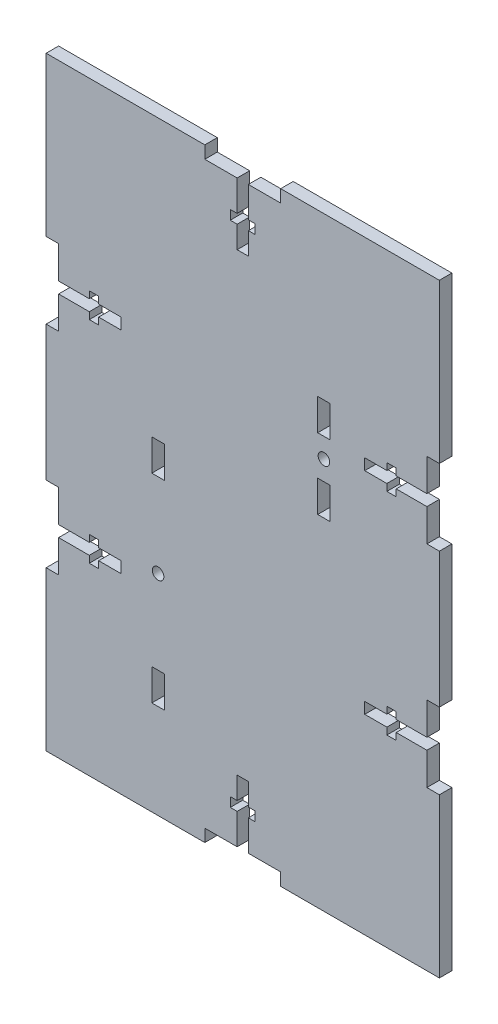
SolidWorks part; units mm, degrees
ref_plane "Front Plane" through (0, 0, 0) normal (0, 0, 1) x (1, 0, 0)
ref_plane "Top Plane" through (0, 0, 0) normal (0, 1, 0) x (1, 0, 0)
ref_plane "Right Plane" through (0, 0, 0) normal (1, 0, 0) x (0, 0, -1)
sketch "Sketch1" plane through (0, 0, 0) normal (0, 0, 1) x (1, 0, 0)
  line L0 (-50, 76.825) -> (-16.6667, 76.825)
  line L1 (-50, -76.825) -> (50, -76.825)
  line L2 (-50, -76.825) -> (-50, 76.825)
  line L3 (-50, 76.825) -> (50, 76.825) construction
  line L4 (50, -76.825) -> (50, 76.825)
  line L5 (-50, -76.825) -> (50, 76.825) construction
  line L6 (-50, 76.825) -> (50, -76.825) construction
  line L7 (-16.6667, 76.825) -> (16.6667, 76.825)
  line L8 (16.6667, 76.825) -> (50, 76.825)
  point P0 (0, 0)
  dimension "D1" = 100
  dimension "D2" = 153.65
extrude "Boss-Extrude1" add sketch "Sketch1" along normal blind 3.18
sketch "Sketch3" [suppressed] plane through (0, 0, 0) normal (0, 0, -1) x (-1, 0, 0)
  line L0 (-32.675, 34.075) -> (-32.675, -61.675)
  line L1 (-32.675, -61.675) -> (32.675, -61.675)
  line L2 (32.675, -61.675) -> (32.675, 34.075)
  line L3 (32.675, 34.075) -> (9.5, 34.075)
  line L4 (9.5, 34.075) -> (9.5, 37.075)
  line L5 (9.5, 37.075) -> (-9.5, 37.075)
  line L6 (-9.5, 37.075) -> (-9.5, 34.075)
  line L7 (-9.5, 34.075) -> (-32.675, 34.075)
  line L8 (32.675, 44.075) -> (-32.675, 44.075)
  line L9 (32.675, -61.675) -> (32.675, 44.075)
  line L10 (-32.675, -61.675) -> (32.675, -61.675)
  line L11 (-32.675, 44.075) -> (-32.675, -61.675)
  line L12 (-32.675, -61.675) -> (-32.675, -73.645) construction
  line L13 (44.645, -73.645) -> (-44.645, -73.645) construction
  line L14 (-32.675, -61.675) -> (-44.645, -61.675) construction
  line L15 (-44.645, -73.645) -> (-44.645, 73.645) construction
  line L16 (32.675, -61.675) -> (44.645, -61.675) construction
  line L17 (44.645, 73.645) -> (44.645, -73.645) construction
  dimension "D1" = 65.35
  dimension "D2" = 95.75
  dimension "D3" = 105.75
  dimension "D4" = 19
  dimension "D5" = 3
extrude "Cut-Extrude1" [suppressed] cut sketch "Sketch3" against normal through all contours L6 L7 L0 L1 L2 L3 L4 L5
sketch "Sketch9" [suppressed] plane through (-44.645, 0, 0) normal (-1, 0, 0) x (0, 0, 1)
  line L0 (0, 0) -> (3.18, 0) construction
  line L1 (0, 73.645) -> (0, -73.645) construction
  line L2 (3.18, 73.645) -> (3.18, -73.645) construction
  line L4 (0, -9.65) -> (3.18, -9.65)
  line L5 (0, -9.65) -> (0, 9.65)
  line L6 (0, 9.65) -> (3.18, 9.65)
  line L7 (3.18, -9.65) -> (3.18, 9.65)
  line L8 (0, -9.65) -> (3.18, 9.65) construction
  line L9 (0, 9.65) -> (3.18, -9.65) construction
  point P6 (1.59, 0)
  dimension "D1" = 19.3
extrude "Boss-Extrude4" [suppressed] add sketch "Sketch9" along normal blind 3.18
sketch "Sketch10" [suppressed] plane through (0, 0, 3.18) normal (0, 0, 1) x (1, 0, 0)
  line L0 (-46.235, 9.65) -> (-46.235, -9.65) construction
  line L1 (-47.825, 9.65) -> (-44.645, 9.65) construction
  line L2 (-47.825, -9.65) -> (-44.645, -9.65) construction
  circle A0 centre (-46.235, 0) radius 1.425
extrude "Cut-Extrude4" [suppressed] cut sketch "Sketch10" against normal through all
mirror "Mirror1" [suppressed] about plane through (0, 0, 0) normal (1, 0, 0)
sketch "Sketch18" [suppressed] plane through (44.645, 0, 0) normal (1, 0, 0) x (0, 0, -1)
  line L0 (0, 0) -> (-3.18, 0) construction
  line L1 (0, -73.645) -> (0, 73.645) construction
  line L2 (-3.18, -73.645) -> (-3.18, 73.645) construction
  line L4 (-3.18, -9.65) -> (0, -9.65)
  line L5 (-3.18, -9.65) -> (-3.18, 9.65)
  line L6 (-3.18, 9.65) -> (0, 9.65)
  line L7 (0, -9.65) -> (0, 9.65)
  line L8 (-3.18, -9.65) -> (0, 9.65) construction
  line L9 (-3.18, 9.65) -> (0, -9.65) construction
  point P6 (-1.59, 0)
  dimension "D1" = 19.3
extrude "Boss-Extrude8" [suppressed] add sketch "Sketch18" along normal blind 3.18
sketch "Sketch19" [suppressed] plane through (0, 0, 3.18) normal (0, 0, 1) x (1, 0, 0)
  line L0 (46.235, -9.65) -> (46.235, 9.65) construction
  line L1 (47.825, -9.65) -> (44.645, -9.65) construction
  line L2 (47.825, 9.65) -> (44.645, 9.65) construction
  circle A0 centre (46.235, 0) radius 1.425
extrude "Cut-Extrude8" [suppressed] cut sketch "Sketch19" against normal through all
mirror "Mirror2" [suppressed] about plane through (0, 0, 0) normal (1, 0, 0)
sketch "Sketch20" plane through (0, 0, 3.18) normal (0, 0, 1) x (1, 0, 0)
  line L0 (0, 70.465) -> (0, 0) construction
  line L1 (50, 76.825) -> (-50, 76.825) construction
  line L2 (-9.65, 76.825) -> (9.65, 76.825)
  line L3 (9.65, 76.825) -> (9.65, 73.645)
  line L4 (9.65, 73.645) -> (1.425, 73.645)
  line L5 (1.425, 73.645) -> (1.425, 65.845)
  line L6 (1.425, 65.845) -> (3.175, 65.845)
  line L7 (3.175, 65.845) -> (3.175, 63.465)
  line L8 (3.175, 63.465) -> (1.425, 63.465)
  line L9 (1.425, 63.465) -> (1.425, 57.845)
  line L10 (1.425, 57.845) -> (-1.425, 57.845)
  line L11 (-1.425, 57.845) -> (-1.425, 63.465)
  line L12 (-1.425, 63.465) -> (-3.175, 63.465)
  line L13 (-3.175, 63.465) -> (-3.175, 65.845)
  line L14 (-3.175, 65.845) -> (-1.425, 65.845)
  line L15 (-1.425, 65.845) -> (-1.425, 73.645)
  line L16 (-1.425, 73.645) -> (-9.65, 73.645)
  line L17 (-9.65, 73.645) -> (-9.65, 76.825)
  dimension "D1" = 19.3
  dimension "D2" = 3.18
  dimension "D3" = 15.8
  dimension "D4" = 6.35
  dimension "D5" = 2.38
  dimension "D6" = 2.85
  dimension "D7" = 7.8
extrude "Cut-Extrude9" cut sketch "Sketch20" against normal through all
mirror "Mirror3" about plane through (0, 0, 0) normal (0, 1, 0) of "Cut-Extrude9"
sketch "Sketch23" plane through (0, 0, 3.18) normal (0, 0, 1) x (1, 0, 0)
  line L0 (-50, 17.175) -> (-50, 36.475)
  line L1 (-50, 76.825) -> (-50, -76.825) construction
  line L2 (-50, 36.475) -> (-46.82, 36.475)
  line L3 (-46.82, 36.475) -> (-46.82, 28.25)
  line L4 (-46.82, 28.25) -> (-39.02, 28.25)
  line L5 (-39.02, 28.25) -> (-39.02, 30)
  line L6 (-39.02, 30) -> (-36.64, 30)
  line L7 (-36.64, 30) -> (-36.64, 28.25)
  line L8 (-36.64, 28.25) -> (-31.02, 28.25)
  line L9 (-31.02, 28.25) -> (-31.02, 25.4)
  line L10 (-31.02, 25.4) -> (-36.64, 25.4)
  line L11 (-36.64, 25.4) -> (-36.64, 23.65)
  line L12 (-36.64, 23.65) -> (-39.02, 23.65)
  line L13 (-39.02, 23.65) -> (-39.02, 25.4)
  line L14 (-39.02, 25.4) -> (-46.82, 25.4)
  line L15 (-46.82, 25.4) -> (-46.82, 17.175)
  line L16 (-46.82, 17.175) -> (-50, 17.175)
  line L17 (-9.65, 76.825) -> (-50, 76.825) construction
  line L19 (-31.02, 26.825) -> (-50, 26.825) construction
  line L20 (-50, -36.475) -> (-50, -17.175)
  line L21 (-50, -17.175) -> (-46.82, -17.175)
  line L22 (-46.82, -17.175) -> (-46.82, -25.4)
  line L23 (-46.82, -25.4) -> (-39.02, -25.4)
  line L24 (-39.02, -25.4) -> (-39.02, -23.65)
  line L25 (-39.02, -23.65) -> (-36.64, -23.65)
  line L26 (-36.64, -23.65) -> (-36.64, -25.4)
  line L27 (-36.64, -25.4) -> (-31.02, -25.4)
  line L28 (-31.02, -25.4) -> (-31.02, -28.25)
  line L29 (-31.02, -28.25) -> (-36.64, -28.25)
  line L30 (-36.64, -28.25) -> (-36.64, -30)
  line L31 (-36.64, -30) -> (-39.02, -30)
  line L32 (-39.02, -30) -> (-39.02, -28.25)
  line L33 (-39.02, -28.25) -> (-46.82, -28.25)
  line L34 (-46.82, -28.25) -> (-46.82, -36.475)
  line L35 (-46.82, -36.475) -> (-50, -36.475)
  line L36 (-50, -26.825) -> (-31.02, -26.825) construction
  line L37 (-50, -76.825) -> (-9.65, -76.825) construction
  dimension "D1" = 50
  dimension "D2" = 19.3
  dimension "D3" = 3.18
  dimension "D4" = 15.8
  dimension "D5" = 6.35
  dimension "D6" = 2.85
  dimension "D7" = 7.8
  dimension "D8" = 2.38
  dimension "D9" = 19.3
  dimension "D10" = 3.18
  dimension "D11" = 7.8
  dimension "D12" = 15.8
  dimension "D13" = 6.35
  dimension "D14" = 2.85
  dimension "D15" = 2.38
  dimension "D16" = 50
  dimension "D17" = 1.75
extrude "Cut-Extrude10" cut sketch "Sketch23" against normal through all
sketch "Sketch24" [suppressed] plane through (0, 0, 3.18) normal (0, 0, 1) x (1, 0, 0)
  line L0 (44.645, -13.995) -> (44.645, -33.295)
  line L1 (44.645, -73.645) -> (44.645, 73.645) construction
  line L2 (44.645, -33.295) -> (41.465, -33.295)
  line L3 (41.465, -33.295) -> (41.465, -25.07)
  line L4 (41.465, -25.07) -> (33.665, -25.07)
  line L5 (33.665, -25.07) -> (33.665, -26.82)
  line L6 (33.665, -26.82) -> (31.285, -26.82)
  line L7 (31.285, -26.82) -> (31.285, -25.07)
  line L8 (31.285, -25.07) -> (25.665, -25.07)
  line L9 (25.665, -25.07) -> (25.665, -22.22)
  line L10 (25.665, -22.22) -> (31.285, -22.22)
  line L11 (31.285, -22.22) -> (31.285, -20.47)
  line L12 (31.285, -20.47) -> (33.665, -20.47)
  line L13 (33.665, -20.47) -> (33.665, -22.22)
  line L14 (33.665, -22.22) -> (41.465, -22.22)
  line L15 (41.465, -22.22) -> (41.465, -13.995)
  line L16 (41.465, -13.995) -> (44.645, -13.995)
  line L17 (25.665, -23.645) -> (44.645, -23.645) construction
  line L18 (-44.645, -73.645) -> (44.645, -73.645) construction
  line L19 (44.645, 33.295) -> (44.645, 13.995)
  line L20 (44.645, 13.995) -> (41.465, 13.995)
  line L21 (41.465, 13.995) -> (41.465, 22.22)
  line L22 (41.465, 22.22) -> (33.665, 22.22)
  line L23 (33.665, 22.22) -> (33.665, 20.47)
  line L24 (33.665, 20.47) -> (31.285, 20.47)
  line L25 (31.285, 20.47) -> (31.285, 22.22)
  line L26 (31.285, 22.22) -> (25.665, 22.22)
  line L27 (25.665, 22.22) -> (25.665, 25.07)
  line L28 (25.665, 25.07) -> (31.285, 25.07)
  line L29 (31.285, 25.07) -> (31.285, 26.82)
  line L30 (31.285, 26.82) -> (33.665, 26.82)
  line L31 (33.665, 26.82) -> (33.665, 25.07)
  line L32 (33.665, 25.07) -> (41.465, 25.07)
  line L33 (41.465, 25.07) -> (41.465, 33.295)
  line L34 (41.465, 33.295) -> (44.645, 33.295)
  line L35 (25.665, 23.645) -> (44.645, 23.645) construction
  line L36 (44.645, 73.645) -> (-44.645, 73.645) construction
  dimension "D1" = 19.3
  dimension "D2" = 3.18
  dimension "D3" = 15.8
  dimension "D4" = 7.8
  dimension "D5" = 6.35
  dimension "D6" = 2.85
  dimension "D7" = 2.38
  dimension "D8" = 50
  dimension "D9" = 19.3
  dimension "D10" = 3.18
  dimension "D11" = 7.8
  dimension "D12" = 15.8
  dimension "D13" = 6.35
  dimension "D14" = 2.85
  dimension "D15" = 2.38
  dimension "D16" = 50
extrude "Cut-Extrude11" [suppressed] cut sketch "Sketch24" against normal through all
sketch "Sketch25" [suppressed] plane through (0, 0, 3.18) normal (0, 0, 1) x (1, 0, 0)
  line L0 (9.65, -73.645) -> (-9.65, -73.645)
  line L1 (-44.645, -73.645) -> (44.645, -73.645) construction
  line L2 (-9.65, -73.645) -> (-9.65, -70.465)
  line L3 (-9.65, -70.465) -> (-1.425, -70.465)
  line L4 (-1.425, -70.465) -> (-1.425, -62.665)
  line L5 (-1.425, -62.665) -> (-3.175, -62.665)
  line L6 (-3.175, -62.665) -> (-3.175, -60.285)
  line L7 (-3.175, -60.285) -> (-1.425, -60.285)
  line L8 (-1.425, -60.285) -> (-1.425, -54.665)
  line L9 (-1.425, -54.665) -> (1.425, -54.665)
  line L10 (1.425, -54.665) -> (1.425, -60.285)
  line L11 (1.425, -60.285) -> (3.175, -60.285)
  line L12 (3.175, -60.285) -> (3.175, -62.665)
  line L13 (3.175, -62.665) -> (1.425, -62.665)
  line L14 (1.425, -62.665) -> (1.425, -70.465)
  line L15 (1.425, -70.465) -> (9.65, -70.465)
  line L16 (9.65, -70.465) -> (9.65, -73.645)
  line L17 (0, -73.645) -> (0, 0) construction
  dimension "D1" = 19.3
  dimension "D2" = 3.18
  dimension "D3" = 15.8
  dimension "D4" = 7.8
  dimension "D5" = 6.35
  dimension "D6" = 2.85
  dimension "D7" = 2.38
extrude "Cut-Extrude12" [suppressed] cut sketch "Sketch25" against normal through all
sketch "Sketch26" [suppressed] plane through (0, 0, 3.18) normal (0, 0, 1) x (1, 0, 0)
  line L0 (-9.65, 73.645) -> (9.65, 73.645)
  line L1 (44.645, 73.645) -> (-44.645, 73.645) construction
  line L2 (9.65, 73.645) -> (9.65, 70.465)
  line L3 (9.65, 70.465) -> (1.425, 70.465)
  line L4 (1.425, 70.465) -> (1.425, 62.665)
  line L5 (1.425, 62.665) -> (3.175, 62.665)
  line L6 (3.175, 62.665) -> (3.175, 60.285)
  line L7 (3.175, 60.285) -> (1.425, 60.285)
  line L8 (1.425, 60.285) -> (1.425, 54.665)
  line L9 (1.425, 54.665) -> (-1.425, 54.665)
  line L10 (-1.425, 54.665) -> (-1.425, 60.285)
  line L11 (-1.425, 60.285) -> (-3.175, 60.285)
  line L12 (-3.175, 60.285) -> (-3.175, 62.665)
  line L13 (-3.175, 62.665) -> (-1.425, 62.665)
  line L14 (-1.425, 62.665) -> (-1.425, 70.465)
  line L15 (-1.425, 70.465) -> (-9.65, 70.465)
  line L16 (-9.65, 70.465) -> (-9.65, 73.645)
  line L17 (0, 73.645) -> (0, -4.4192) construction
  dimension "D1" = 19.3
  dimension "D2" = 3.18
  dimension "D3" = 7.8
  dimension "D4" = 15.8
  dimension "D5" = 6.35
  dimension "D6" = 2.85
  dimension "D7" = 2.38
extrude "Cut-Extrude13" [suppressed] cut sketch "Sketch26" against normal through all
mirror "Mirror4" about plane through (0, 0, 0) normal (1, 0, 0) of "Cut-Extrude10"
mirror "Mirror5" [suppressed] about plane through (0, 0, 0) normal (1, 0, 0)
mirror "Mirror6" [suppressed] about plane through (0, 0, 0) normal (0, 1, 0)
mirror "Mirror7" [suppressed] about plane through (0, 0, 0) normal (0, 1, 0)
sketch "Sketch27" [suppressed] plane through (-44.645, 0, 0) normal (-1, 0, 0) x (0, 0, 1)
  line L0 (0, -36.475) -> (0, -17.175)
  line L1 (0, 73.645) -> (0, -73.645) construction
  line L2 (0, -17.175) -> (3.18, -17.175)
  line L3 (3.18, 73.645) -> (3.18, -73.645) construction
  line L4 (3.18, -17.175) -> (3.18, -36.475)
  line L5 (3.18, -36.475) -> (0, -36.475)
  line L6 (3.18, -26.825) -> (0, -26.825) construction
  line L7 (3.18, -73.645) -> (0, -73.645) construction
  dimension "D1" = 19.3
  dimension "D2" = 46.82
extrude "Boss-Extrude9" [suppressed] add sketch "Sketch27" along normal blind 3.18
sketch "Sketch28" [suppressed] plane through (0, -73.645, 0) normal (0, -1, 0) x (1, 0, 0)
  line L0 (9.65, 0) -> (-9.65, 0)
  line L1 (-44.645, 0) -> (44.645, 0) construction
  line L2 (-9.65, 0) -> (-9.65, 3.18)
  line L3 (-44.645, 3.18) -> (44.645, 3.18) construction
  line L4 (-9.65, 3.18) -> (9.65, 3.18)
  line L5 (9.65, 3.18) -> (9.65, 0)
  line L6 (0, 0) -> (0, 3.18) construction
  dimension "D1" = 19.3
extrude "Boss-Extrude10" [suppressed] add sketch "Sketch28" along normal blind 3.18
sketch "Sketch29" [suppressed] plane through (0, 0, 3.18) normal (0, 0, 1) x (1, 0, 0)
  line L0 (-47.825, -26.825) -> (-37.3062, -26.825) construction
  line L1 (-47.825, -36.475) -> (-47.825, -17.175) construction
  line L2 (-46.235, -17.175) -> (-46.235, -36.475) construction
  line L3 (-47.825, -17.175) -> (-44.645, -17.175) construction
  line L4 (-47.825, -36.475) -> (-44.645, -36.475) construction
  circle A0 centre (-46.235, -26.825) radius 1.425
extrude "Cut-Extrude14" [suppressed] cut sketch "Sketch29" against normal through all
sketch "Sketch30" [suppressed] plane through (0, 0, 3.18) normal (0, 0, 1) x (1, 0, 0)
  line L0 (0, -76.825) -> (0, -66.2855) construction
  line L1 (9.65, -76.825) -> (-9.65, -76.825) construction
  line L2 (9.65, -75.235) -> (-9.65, -75.235) construction
  line L3 (9.65, -76.825) -> (9.65, -73.645) construction
  line L4 (-9.65, -76.825) -> (-9.65, -73.645) construction
  circle A0 centre (0, -75.235) radius 1.425
extrude "Cut-Extrude15" [suppressed] cut sketch "Sketch30" against normal through all
mirror "Mirror8" [suppressed] about plane through (0, 0, 0) normal (1, 0, 0)
mirror "Mirror9" [suppressed] about plane through (0, 0, 0) normal (0, 1, 0)
sketch "Sketch31" [suppressed] plane through (0, 0, 3.18) normal (0, 0, 1) x (1, 0, 0)
  line L0 (14.341, -8.1358) -> (14.341, -12.6358) construction
  line L8 (5.175, -1.9558) -> (5.175, 19.3642) construction
  line L10 (-24.825, 19.3642) -> (-24.825, -1.9558) construction
  line L11 (5.175, 19.3642) -> (-24.825, 19.3642) construction
  line L16 (23.507, -9.6358) -> (39.341, -9.6358) construction
  line L17 (23.507, 19.3642) -> (23.507, -9.6358) construction
  line L18 (39.341, 19.3642) -> (23.507, 19.3642) construction
  line L19 (39.341, -9.6358) -> (39.341, 19.3642) construction
  line L26 (14.341, -15.8158) -> (14.341, -12.6358) construction
  line L29 (-24.825, -1.9558) -> (5.175, -1.9558) construction
  line L34 (20.5772, -7.1358) -> (20.5772, 11.3642) construction
  line L35 (20.5772, 11.3642) -> (8.1048, 11.3642) construction
  line L36 (8.1048, 11.3642) -> (8.1048, -7.1358) construction
  line L37 (9.7431, -8.1358) -> (18.9389, -8.1358) construction
  line L38 (14.341, -15.8158) -> (14.341, -50) construction
  line L39 (-17.325, 9.65) -> (-24.825, 9.65) construction
  line L40 (-6.159, -12.4758) -> (34.841, -12.4758)
  line L41 (-6.159, -12.4758) -> (-6.159, -15.9758)
  line L42 (-6.159, -15.9758) -> (34.841, -15.9758)
  line L43 (34.841, -12.4758) -> (34.841, -15.9758)
  line L88 (-44.645, -50) -> (-9.65, -50) construction
  line L89 (-9.65, -50) -> (-9.65, -46.82) construction
  line L90 (-9.65, -46.82) -> (-1.425, -46.82) construction
  line L91 (-1.425, -46.82) -> (-1.425, -39.02) construction
  line L92 (-1.425, -39.02) -> (-3.175, -39.02) construction
  line L93 (-3.175, -39.02) -> (-3.175, -36.64) construction
  line L94 (-3.175, -36.64) -> (-1.425, -36.64) construction
  line L95 (-1.425, -36.64) -> (-1.425, -31.02) construction
  line L96 (-1.425, -31.02) -> (1.425, -31.02) construction
  line L97 (1.425, -31.02) -> (1.425, -36.64) construction
  line L98 (1.425, -36.64) -> (3.175, -36.64) construction
  line L99 (3.175, -36.64) -> (3.175, -39.02) construction
  line L100 (3.175, -39.02) -> (1.425, -39.02) construction
  line L101 (1.425, -39.02) -> (1.425, -46.82) construction
  line L102 (1.425, -46.82) -> (9.65, -46.82) construction
  line L103 (9.65, -46.82) -> (9.65, -50) construction
  line L104 (9.65, -50) -> (44.645, -50) construction
  line L105 (44.645, -50) -> (44.645, -9.65) construction
  line L106 (44.645, -9.65) -> (47.825, -9.65) construction
  line L107 (47.825, -9.65) -> (47.825, 9.65) construction
  line L108 (47.825, 9.65) -> (44.645, 9.65) construction
  line L109 (44.645, 9.65) -> (44.645, 50) construction
  line L110 (44.645, 50) -> (9.65, 50) construction
  line L111 (9.65, 50) -> (9.65, 46.82) construction
  line L112 (9.65, 46.82) -> (1.425, 46.82) construction
  line L113 (1.425, 46.82) -> (1.425, 39.02) construction
  line L114 (1.425, 39.02) -> (3.175, 39.02) construction
  line L115 (3.175, 39.02) -> (3.175, 36.64) construction
  line L116 (3.175, 36.64) -> (1.425, 36.64) construction
  line L117 (1.425, 36.64) -> (1.425, 31.02) construction
  line L118 (1.425, 31.02) -> (-1.425, 31.02) construction
  line L119 (-1.425, 31.02) -> (-1.425, 36.64) construction
  line L120 (-1.425, 36.64) -> (-3.175, 36.64) construction
  line L121 (-3.175, 36.64) -> (-3.175, 39.02) construction
  line L122 (-3.175, 39.02) -> (-1.425, 39.02) construction
  line L123 (-1.425, 39.02) -> (-1.425, 46.82) construction
  line L124 (-1.425, 46.82) -> (-9.65, 46.82) construction
  line L125 (-9.65, 46.82) -> (-9.65, 50) construction
  line L126 (-9.65, 50) -> (-44.645, 50) construction
  line L127 (-44.645, 50) -> (-44.645, 9.65) construction
  line L128 (-44.645, 9.65) -> (-47.825, 9.65) construction
  line L129 (-47.825, 9.65) -> (-47.825, -9.65) construction
  line L130 (-47.825, -9.65) -> (-44.645, -9.65) construction
  line L131 (-44.645, -9.65) -> (-44.645, -50) construction
  line L132 (-6.159, -12.4758) -> (34.841, -15.9758) construction
  line L133 (-6.159, -15.9758) -> (34.841, -12.4758) construction
  line L134 (-17.325, 9.65) -> (-17.325, -1.9558) construction
  line L135 (31.3061, 4.8642) -> (39.341, 4.8642) construction
  line L136 (31.3061, 4.8642) -> (31.3061, 19.3642) construction
  line L137 (-17.325, 9.65) -> (-4.325, 9.65) construction
  circle A0 centre (-17.325, 9.65) radius 1.5
  circle A1 centre (31.3061, 4.8642) radius 1.5
  circle A2 centre (-4.325, 9.65) radius 1.5
  spline S4 degree 3 poles (8.1048, -7.1358) (8.1048, -7.3148) (8.1799, -7.485) (8.4092, -7.7556) (8.5582, -7.8571) (8.8762, -8.0081) (9.0479, -8.0586) (9.3919, -8.1221) (9.5665, -8.1358) (9.7431, -8.1358) knots 0 0 0 0 0.25 0.25 0.5 0.5 0.75 0.75 1 1 1 1 construction
  spline S5 degree 3 poles (18.9389, -8.1358) (19.1156, -8.1358) (19.2906, -8.1221) (19.6363, -8.0581) (19.8071, -8.0076) (20.1239, -7.857) (20.2729, -7.7556) (20.5025, -7.4843) (20.5772, -7.3148) (20.5772, -7.1358) knots 0 0 0 0 0.25 0.25 0.5 0.5 0.75 0.75 1 1 1 1 construction
  point P14 (14.341, -14.2258)
  point P46 (-44.645, 73.645)
  dimension "D6" = 3
  dimension "D4" = 41
  dimension "D5" = 3.5
  dimension "D7" = 7.5
  dimension "D9" = 13
extrude "Cut-Extrude16" [suppressed] cut sketch "Sketch31" against normal through all contours L41 L40 L43 L42 | A1 | A2 | A0
sketch "Sketch32" plane through (0, 0, 3.18) normal (0, 0, 1) x (1, 0, 0)
  line L0 (22.24, 17.7829) -> (22.24, 9.7829)
  line L1 (22.24, 35.7829) -> (22.24, 27.7829)
  line L2 (22.24, 35.7829) -> (19.06, 35.7829)
  line L3 (22.24, 35.7829) -> (22.24, 27.7829)
  line L4 (22.24, 27.7829) -> (19.06, 27.7829)
  line L5 (19.06, 35.7829) -> (19.06, 27.7829)
  line L6 (22.24, 17.7829) -> (19.06, 17.7829)
  line L7 (22.24, 17.7829) -> (22.24, 9.7829)
  line L8 (22.24, 9.7829) -> (19.06, 9.7829)
  line L9 (19.06, 17.7829) -> (19.06, 9.7829)
  line L10 (22.24, 17.7829) -> (22.24, 27.7829) construction
  line L11 (50, -17.175) -> (50, 17.175) construction
  line L12 (50, 17.175) -> (46.82, 17.175) construction
  line L13 (46.82, 17.175) -> (46.82, 25.4) construction
  line L14 (46.82, 25.4) -> (39.02, 25.4) construction
  line L15 (39.02, 25.4) -> (39.02, 23.65) construction
  line L16 (39.02, 23.65) -> (36.64, 23.65) construction
  line L17 (36.64, 23.65) -> (36.64, 25.4) construction
  line L18 (36.64, 25.4) -> (31.02, 25.4) construction
  line L19 (31.02, 25.4) -> (31.02, 28.25) construction
  line L20 (31.02, 28.25) -> (36.64, 28.25) construction
  line L21 (36.64, 28.25) -> (36.64, 30) construction
  line L22 (36.64, 30) -> (39.02, 30) construction
  line L23 (39.02, 30) -> (39.02, 28.25) construction
  line L24 (39.02, 28.25) -> (46.82, 28.25) construction
  line L25 (46.82, 28.25) -> (46.82, 36.475) construction
  line L26 (46.82, 36.475) -> (50, 36.475) construction
  line L27 (50, 36.475) -> (50, 76.825) construction
  line L28 (50, 76.825) -> (9.65, 76.825) construction
  line L29 (9.65, 76.825) -> (9.65, 73.645) construction
  line L30 (9.65, 73.645) -> (1.425, 73.645) construction
  line L31 (1.425, 73.645) -> (1.425, 65.845) construction
  line L32 (1.425, 65.845) -> (3.175, 65.845) construction
  line L33 (3.175, 65.845) -> (3.175, 63.465) construction
  line L34 (3.175, 63.465) -> (1.425, 63.465) construction
  line L35 (1.425, 63.465) -> (1.425, 57.845) construction
  line L36 (1.425, 57.845) -> (-1.425, 57.845) construction
  line L37 (-1.425, 57.845) -> (-1.425, 63.465) construction
  line L38 (-1.425, 63.465) -> (-3.175, 63.465) construction
  line L39 (-3.175, 63.465) -> (-3.175, 65.845) construction
  line L40 (-3.175, 65.845) -> (-1.425, 65.845) construction
  line L41 (-1.425, 65.845) -> (-1.425, 73.645) construction
  line L42 (-1.425, 73.645) -> (-9.65, 73.645) construction
  line L43 (-9.65, 73.645) -> (-9.65, 76.825) construction
  line L44 (-9.65, 76.825) -> (-50, 76.825) construction
  line L45 (-50, 76.825) -> (-50, 36.475) construction
  line L46 (-50, 36.475) -> (-46.82, 36.475) construction
  line L47 (-46.82, 36.475) -> (-46.82, 28.25) construction
  line L48 (-46.82, 28.25) -> (-39.02, 28.25) construction
  line L49 (-39.02, 28.25) -> (-39.02, 30) construction
  line L50 (-39.02, 30) -> (-36.64, 30) construction
  line L51 (-36.64, 30) -> (-36.64, 28.25) construction
  line L52 (-36.64, 28.25) -> (-31.02, 28.25) construction
  line L53 (-31.02, 28.25) -> (-31.02, 25.4) construction
  line L54 (-31.02, 25.4) -> (-36.64, 25.4) construction
  line L55 (-36.64, 25.4) -> (-36.64, 23.65) construction
  line L56 (-36.64, 23.65) -> (-39.02, 23.65) construction
  line L57 (-39.02, 23.65) -> (-39.02, 25.4) construction
  line L58 (-39.02, 25.4) -> (-46.82, 25.4) construction
  line L59 (-46.82, 25.4) -> (-46.82, 17.175) construction
  line L60 (-46.82, 17.175) -> (-50, 17.175) construction
  line L61 (-50, 17.175) -> (-50, -17.175) construction
  line L62 (-50, -17.175) -> (-46.82, -17.175) construction
  line L63 (-46.82, -17.175) -> (-46.82, -25.4) construction
  line L64 (-46.82, -25.4) -> (-39.02, -25.4) construction
  line L65 (-39.02, -25.4) -> (-39.02, -23.65) construction
  line L66 (-39.02, -23.65) -> (-36.64, -23.65) construction
  line L67 (-36.64, -23.65) -> (-36.64, -25.4) construction
  line L68 (-36.64, -25.4) -> (-31.02, -25.4) construction
  line L69 (-31.02, -25.4) -> (-31.02, -28.25) construction
  line L70 (-31.02, -28.25) -> (-36.64, -28.25) construction
  line L71 (-36.64, -28.25) -> (-36.64, -30) construction
  line L72 (-36.64, -30) -> (-39.02, -30) construction
  line L73 (-39.02, -30) -> (-39.02, -28.25) construction
  line L74 (-39.02, -28.25) -> (-46.82, -28.25) construction
  line L75 (-46.82, -28.25) -> (-46.82, -36.475) construction
  line L76 (-46.82, -36.475) -> (-50, -36.475) construction
  line L77 (-50, -36.475) -> (-50, -76.825) construction
  line L78 (-50, -76.825) -> (-9.65, -76.825) construction
  line L79 (-9.65, -76.825) -> (-9.65, -73.645) construction
  line L80 (-9.65, -73.645) -> (-1.425, -73.645) construction
  line L81 (-1.425, -73.645) -> (-1.425, -65.845) construction
  line L82 (-1.425, -65.845) -> (-3.175, -65.845) construction
  line L83 (-3.175, -65.845) -> (-3.175, -63.465) construction
  line L84 (-3.175, -63.465) -> (-1.425, -63.465) construction
  line L85 (-1.425, -63.465) -> (-1.425, -57.845) construction
  line L86 (-1.425, -57.845) -> (1.425, -57.845) construction
  line L87 (1.425, -57.845) -> (1.425, -63.465) construction
  line L88 (1.425, -63.465) -> (3.175, -63.465) construction
  line L89 (3.175, -63.465) -> (3.175, -65.845) construction
  line L90 (3.175, -65.845) -> (1.425, -65.845) construction
  line L91 (1.425, -65.845) -> (1.425, -73.645) construction
  line L92 (1.425, -73.645) -> (9.65, -73.645) construction
  line L93 (9.65, -73.645) -> (9.65, -76.825) construction
  line L94 (9.65, -76.825) -> (50, -76.825) construction
  line L95 (50, -76.825) -> (50, -36.475) construction
  line L96 (50, -36.475) -> (46.82, -36.475) construction
  line L97 (46.82, -36.475) -> (46.82, -28.25) construction
  line L98 (46.82, -28.25) -> (39.02, -28.25) construction
  line L99 (39.02, -28.25) -> (39.02, -30) construction
  line L100 (39.02, -30) -> (36.64, -30) construction
  line L101 (36.64, -30) -> (36.64, -28.25) construction
  line L102 (36.64, -28.25) -> (31.02, -28.25) construction
  line L103 (31.02, -28.25) -> (31.02, -25.4) construction
  line L104 (31.02, -25.4) -> (36.64, -25.4) construction
  line L105 (36.64, -25.4) -> (36.64, -23.65) construction
  line L106 (36.64, -23.65) -> (39.02, -23.65) construction
  line L107 (39.02, -23.65) -> (39.02, -25.4) construction
  line L108 (39.02, -25.4) -> (46.82, -25.4) construction
  line L109 (46.82, -25.4) -> (46.82, -17.175) construction
  line L110 (46.82, -17.175) -> (50, -17.175) construction
  line L111 (20.65, 27.7829) -> (20.65, 17.7829) construction
  line L112 (0, 0) -> (0, 57.845) construction
  line L113 (-20.65, 27.7829) -> (-20.65, 17.7829) construction
  line L114 (-22.24, 17.7829) -> (-22.24, 27.7829) construction
  line L115 (-19.06, 17.7829) -> (-19.06, 9.7829)
  line L116 (-22.24, 9.7829) -> (-19.06, 9.7829)
  line L117 (-22.24, 17.7829) -> (-22.24, 9.7829)
  line L118 (-22.24, 17.7829) -> (-19.06, 17.7829)
  line L119 (-19.06, 35.7829) -> (-19.06, 27.7829)
  line L120 (-22.24, 27.7829) -> (-19.06, 27.7829)
  line L121 (-22.24, 35.7829) -> (-22.24, 27.7829)
  line L122 (-22.24, 35.7829) -> (-19.06, 35.7829)
  line L123 (-22.24, 35.7829) -> (-22.24, 27.7829)
  line L124 (-22.24, 17.7829) -> (-22.24, 9.7829)
  circle A0 centre (20.65, 22.7829) radius 1.47
  circle A1 centre (-20.65, 22.7829) radius 1.47
  dimension "D1" = 2.94
extrude "Cut-Extrude17" [suppressed] cut sketch "Sketch32" against normal through all contours L118 L117 L116 L115 | L122 L121 L120 L119 | A1
extrude "Cut-Extrude18" cut sketch "Sketch32<4>" against normal through all contours L2 L5 L4 L1 | A0 | L6 L9 L8 L0 region at (20.65, 13.7829, 3.18) region at (20.65, 31.7829, 3.18) region at (20.65, 22.7829, 3.18)
sketch "Sketch32<4>" plane through (0, 0, 3.18) normal (0, 0, 1) x (1, 0, 0) same geometry as "Sketch32"
sketch "Sketch33" plane through (0, 0, 0) normal (0, 0, 1) x (1, 0, 0)
  line L0 (0, -1.749) -> (0, 1.749) construction
  line L1 (19.94, 5.7884) -> (23.12, 5.7884)
  line L2 (19.94, -2.2116) -> (19.94, 5.7884)
  line L3 (23.12, -2.2116) -> (19.94, -2.2116)
  line L4 (23.12, 5.7884) -> (23.12, -2.2116)
  line L5 (19.94, -44.8116) -> (23.12, -44.8116)
  line L6 (19.94, -52.8116) -> (19.94, -44.8116)
  line L7 (23.12, -52.8116) -> (19.94, -52.8116)
  line L8 (23.12, -44.8116) -> (23.12, -52.8116)
  line L9 (-21.53, -2.2116) -> (-21.53, -44.8116) construction
  line L10 (21.53, -2.2116) -> (21.53, -44.8116) construction
  line L108 (-23.12, -44.8116) -> (-23.12, -52.8116)
  line L109 (-23.12, -52.8116) -> (-19.94, -52.8116)
  line L110 (-19.94, -52.8116) -> (-19.94, -44.8116)
  line L111 (-19.94, -44.8116) -> (-23.12, -44.8116)
  line L112 (-23.12, 5.7884) -> (-23.12, -2.2116)
  line L113 (-23.12, -2.2116) -> (-19.94, -2.2116)
  line L114 (-19.94, -2.2116) -> (-19.94, 5.7884)
  line L115 (-19.94, 5.7884) -> (-23.12, 5.7884)
  circle A0 centre (-21.53, -23.5116) radius 1.47
  circle A1 centre (21.53, -23.5116) radius 1.47
extrude "Cut-Extrude22" cut sketch "Sketch33" along normal through all contours L112 L113 L114 L115 | L108 L109 L110 L111 | A0
